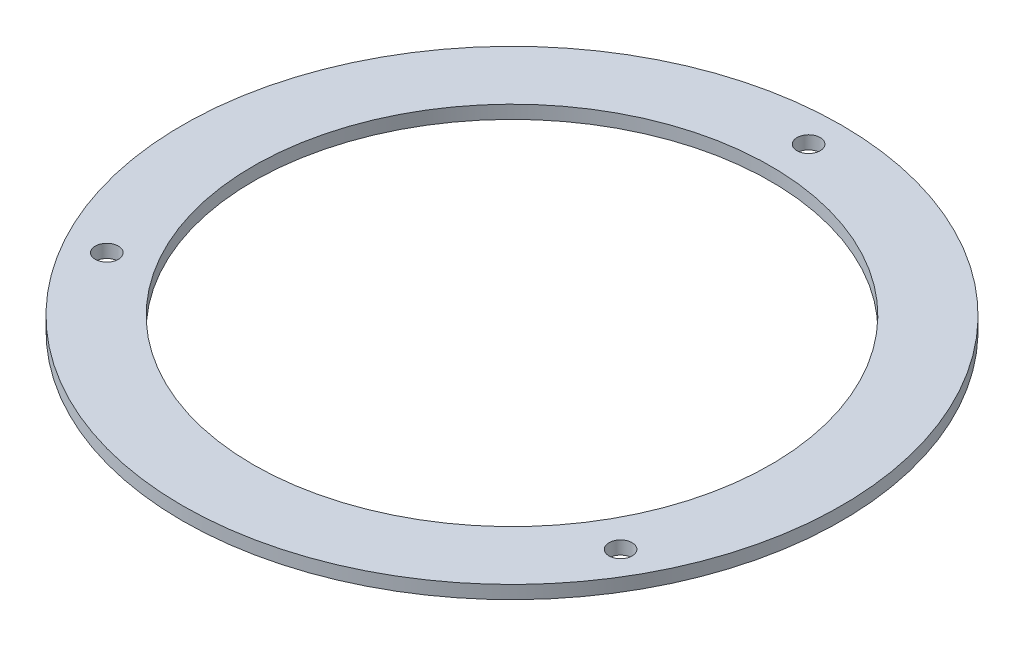
SolidWorks part; units mm, degrees
ref_plane "Front Plane" through (0, 0, 0) normal (0, 0, 1) x (1, 0, 0)
ref_plane "Top Plane" through (0, 0, 0) normal (0, 1, 0) x (1, 0, 0)
ref_plane "Right Plane" through (0, 0, 0) normal (1, 0, 0) x (0, 0, -1)
sketch "Sketch1" plane through (0, 0, 0) normal (0, 1, 0) x (1, 0, 0)
  circle A0 centre (0, 0) radius 39.25
  circle A1 centre (0, 0) radius 50
  circle A2 centre (0, 0) radius 45 construction
  circle A3 centre (0, 45) radius 1.75
  circle A4 centre (38.9711, -22.5) radius 1.75
  circle A5 centre (-38.9711, -22.5) radius 1.75
  point P13 (0, 0)
  dimension "D1" = 100
  dimension "D2" = 78.5
  dimension "D3" = 90
  dimension "D4" = 3.5
  dimension "D5" = 3
extrude "Boss-Extrude1" add sketch "Sketch1" along normal blind 2
